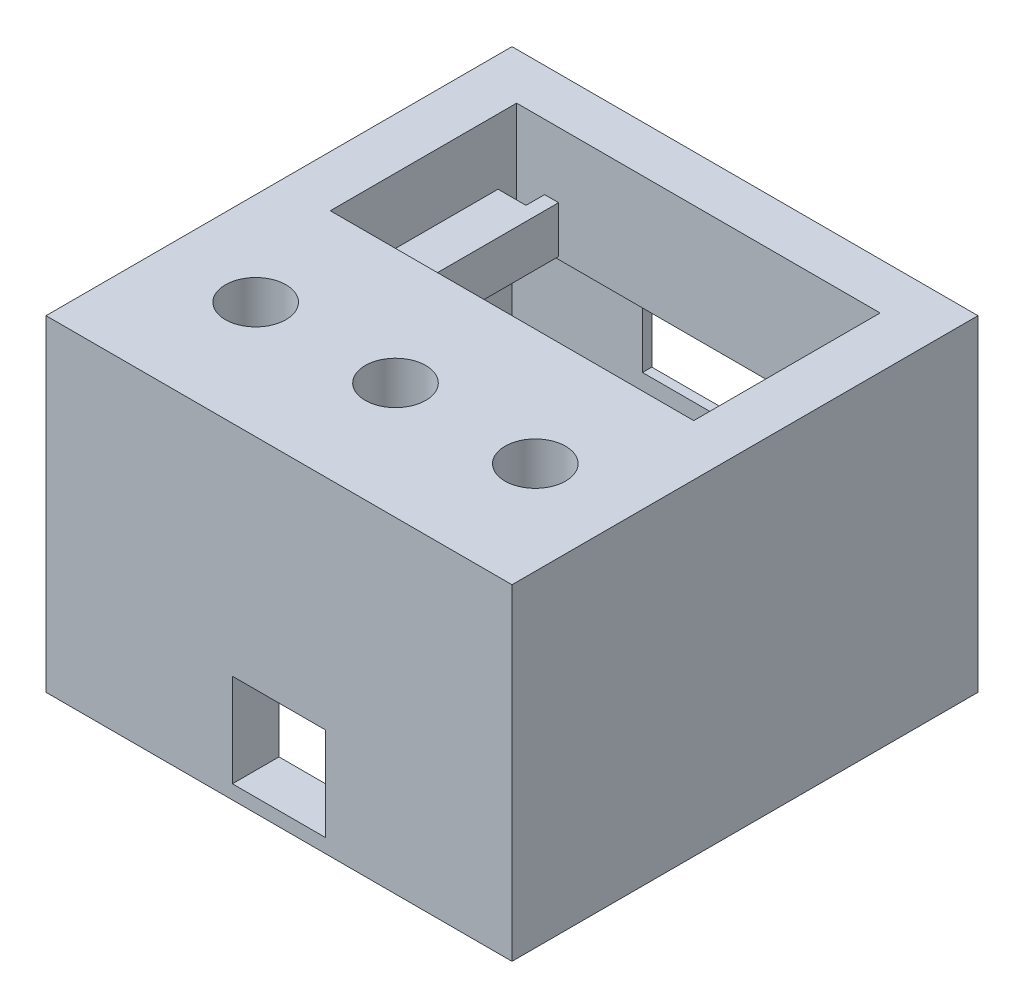
SolidWorks part; units mm, degrees
ref_plane "Front Plane" through (0, 0, 0) normal (0, 0, 1) x (1, 0, 0)
ref_plane "Top Plane" through (0, 0, 0) normal (0, 1, 0) x (1, 0, 0)
ref_plane "Right Plane" through (0, 0, 0) normal (1, 0, 0) x (0, 0, -1)
sketch "Sketch2" plane through (0, 0, 0) normal (0, 1, 0) x (1, 0, 0)
  line L0 (0, 0) -> (0, 25)
  line L1 (-25, 25) -> (25, 25)
  line L2 (-25, 25) -> (-25, -25)
  line L3 (-25, -25) -> (25, -25)
  line L4 (25, 25) -> (25, -25)
  line L5 (-25, 25) -> (25, -25) construction
  line L6 (-25, -25) -> (25, 25) construction
  point P0 (0, 0)
  dimension "D1" = 50
  dimension "D2" = 50
extrude "Boss-Extrude1" add sketch "Sketch2" against normal blind 40 contours L4 L1 L2 L3 region at (-12.5, 0, -24.2929)
sketch "Sketch3" plane through (0, 0, 0) normal (0, 1, 0) x (1, 0, 0)
  line L0 (0, 25) -> (0, 20)
  line L1 (-25, 25) -> (25, 25) construction
  line L2 (0, 20) -> (19.5, 20)
  line L3 (0, 20) -> (-19.5, 20)
  line L4 (-19.5, 20) -> (-19.5, 0)
  line L5 (-19.5, 0) -> (19.5, 0)
  line L6 (19.5, 20) -> (19.5, 0)
sketch "Sketch4" plane through (0, 0, 0) normal (0, 1, 0) x (1, 0, 0)
  line L0 (0, 0) -> (0, -25)
  line L1 (-25, -25) -> (25, -25) construction
  line L2 (0, -12.5) -> (15, -12.5)
  line L3 (0, -12.5) -> (-15, -12.5)
  line L4 (-15, -12.5) -> (-15, -25)
  circle A0 centre (15, -12.5) radius 3.25
  circle A1 centre (-15, -12.5) radius 3.25
  circle A2 centre (0, -12.5) radius 3.25
extrude "Cut-Extrude1" cut sketch "Sketch4" against normal blind 6 contours L0 A2 L3 | L2 A2 L0 | L0 A2 L2 | L3 A2 L0 | A0 | A1 region at (1.3793, 0, 11.1207) region at (15, 0, 9.3419) region at (-1.3793, 0, 11.1207) region at (1.3793, 0, 13.8793) region at (-1.3793, 0, 13.8793)
sketch "Sketch5" plane through (0, -40, 0) normal (0, -1, 0) x (1, 0, 0)
  line L0 (-15, 12.5) -> (-19, 12.5)
  line L1 (-15, 12.5) -> (-11, 12.5)
  line L2 (0, 12.5) -> (-15, 12.5) construction
  line L3 (0, 12.5) -> (-4, 12.5)
  line L4 (0, 0) -> (0, 25) construction
  line L5 (0, 12.5) -> (4, 12.5)
  line L6 (0, 12.5) -> (15, 12.5) construction
  line L7 (4, 12.5) -> (4, 19)
  line L8 (4, 12.5) -> (4, 6)
  line L9 (4, 6) -> (-4, 6)
  line L10 (-4, 6) -> (-4, 19)
  line L11 (-4, 19) -> (4, 19)
  line L12 (15, 12.5) -> (11, 12.5)
  line L13 (15, 12.5) -> (19, 12.5)
  line L14 (19, 12.5) -> (19, 19)
  line L15 (19, 19) -> (11, 19)
  line L16 (11, 19) -> (11, 6)
  line L17 (11, 6) -> (19, 6)
  line L18 (19, 6) -> (19, 12.5)
  line L19 (-11, 12.5) -> (-11, 19)
  line L20 (-11, 19) -> (-19, 19)
  line L21 (-19, 19) -> (-19, 6)
  line L22 (-19, 6) -> (-11, 6)
  line L23 (-11, 6) -> (-11, 12.5)
extrude "Cut-Extrude2" cut sketch "Sketch5" against normal blind 34 contours L17 L18 L13 L12 L16 | L15 L16 L12 L13 L14 | L22 L23 L1 L0 L21 | L20 L21 L0 L1 L19 | L8 L9 L10 L11 L7 region at (-15, -40, 9.25) region at (-15, -40, 15.75) region at (15, -40, 9.25) region at (15, -40, 15.75)
sketch "Sketch6" plane through (0, -40, 0) normal (0, -1, 0) x (1, 0, 0)
  line L0 (-25, 25) -> (25, 25)
  line L1 (25, 25) -> (25, -25)
  line L2 (25, -25) -> (-25, -25)
  line L3 (-25, -25) -> (-25, 25)
  line L4 (-20, -20) -> (-20, 20)
  line L5 (-20, 20) -> (20, 20)
  line L6 (20, 20) -> (20, -20)
  line L7 (20, -20) -> (-20, -20)
  line L8 (0, 0) -> (0, 6)
  line L9 (4, 6) -> (-4, 6) construction
  line L10 (0, 3) -> (20, 3)
  line L11 (0, 3) -> (-20, 3)
  line M9 (19, 19) -> (19, 6)
  line M10 (19, 6) -> (11, 6)
  line M11 (11, 6) -> (11, 19)
  line M12 (11, 19) -> (19, 19)
  line M13 (-11, 19) -> (-11, 6)
  line M14 (-11, 6) -> (-19, 6)
  line M15 (-19, 6) -> (-19, 19)
  line M16 (-19, 19) -> (-11, 19)
  line M21 (4, 19) -> (4, 6)
  line M22 (4, 6) -> (-4, 6)
  line M23 (-4, 6) -> (-4, 19)
  line M24 (-4, 19) -> (4, 19)
  dimension "D1" = 5
extrude "Cut-Extrude3" cut sketch "Sketch6" against normal blind 24 contours L11 L10 L6 L5 L4 M22 M23 M24 M21 M16 M13 M14 M15 M12 M9 M10 M11 region at (-19.5654, -40, 11.5)
extrude "Cut-Extrude4" cut sketch "Sketch3" against normal blind 7 contours L6 L2 L3 L4 L5 region at (0, 0, -10)
sketch "Sketch7" plane through (0, -7, 0) normal (0, 1, 0) x (1, 0, 0)
  line L0 (-19.5, 20) -> (-16.5, 20)
  line L1 (-19.5, 20) -> (19.5, 20) construction
  line L2 (-16.5, 20) -> (-16.5, 18)
  line L3 (-16.5, 18) -> (-19.5, 18)
  line L4 (-19.5, 20) -> (-19.5, 0) construction
  line L5 (-19.5, 18) -> (-19.5, 20)
  line L6 (-19.5, 0) -> (-19.5, 2)
  line L7 (-19.5, 20) -> (-19.5, 0) construction
  line L8 (-19.5, 2) -> (-16.5, 2)
  line L9 (-16.5, 2) -> (-16.5, 0)
  line L10 (-19.5, 0) -> (19.5, 0) construction
  line L11 (-16.5, 0) -> (-19.5, 0)
  line L12 (19.5, 0) -> (19.5, 2)
  line L13 (19.5, 20) -> (19.5, 0) construction
  line L14 (19.5, 2) -> (16.5, 2)
  line L15 (16.5, 2) -> (16.5, 0)
  line L16 (-19.5, 0) -> (19.5, 0) construction
  line L17 (16.5, 0) -> (19.5, 0)
  line L18 (19.5, 20) -> (16.5, 20)
  line L19 (-19.5, 20) -> (19.5, 20) construction
  line L20 (16.5, 20) -> (16.5, 18)
  line L21 (16.5, 18) -> (19.5, 18)
  line L22 (19.5, 18) -> (19.5, 20)
sketch "Sketch8" plane through (0, -40, 0) normal (0, -1, 0) x (1, 0, 0)
  line L0 (-20, 3) -> (-20, -25)
  line L1 (-25, -25) -> (25, -25) construction
  line L2 (-20, -25) -> (-20, -20)
  line L3 (20, 3) -> (20, -25)
  line L4 (20, -25) -> (20, -20)
  line L5 (20, -20) -> (-20, -20)
  line L6 (0, -20) -> (0, 0)
  line L7 (0, 0) -> (20, 0)
  line L8 (20, 0) -> (-20, 0)
  line L9 (0, -20) -> (-15, -20)
  line L10 (-15, -20) -> (-15, 0)
  line L11 (-15, 0) -> (15, 0)
  line L12 (15, 0) -> (15, -20)
  line L13 (15, -20) -> (-15, -20)
  line L14 (-20, 3) -> (20, 3)
  line M9 (20, 3) -> (-20, 3)
extrude "Cut-Extrude5" cut sketch "Sketch8" against normal blind 33 contours L10 L5 L6 L8 | L12 L7 L6 L5 region at (-7.5, -40, -10) region at (7.5, -40, -10)
extrude "Cut-Extrude6" cut sketch "Sketch8<3>" against normal blind 24 contours L5 L10 L8 L0 | L8 L12 L5 L3 region at (-17.5, -40, -10) region at (17.5, -40, -10)
sketch "Sketch8<3>" plane through (0, -40, 0) normal (0, -1, 0) x (1, 0, 0) same geometry as "Sketch8"
extrude "Cut-Extrude7" cut sketch "Sketch8<4>" against normal blind 24 contours L8 L7 L3 L0 M9 region at (0, -40, 1.5)
sketch "Sketch8<4>" plane through (0, -40, 0) normal (0, -1, 0) x (1, 0, 0) same geometry as "Sketch8"
extrude "Cut-Extrude8" cut sketch "Sketch7" against normal blind 10
sketch "Sketch9" plane through (0, -40, 0) normal (0, -1, 0) x (1, 0, 0)
  line L0 (-20, 20) -> (-25, 20)
  line L1 (-25, -25) -> (-25, 25) construction
  line L2 (-25, 20) -> (-25, 25)
  line L3 (-25, 25) -> (-20, 25)
  line L4 (-25, 25) -> (25, 25) construction
  line L5 (-20, 25) -> (-20, 20)
  line L6 (-20, -20) -> (-25, -20)
  line L7 (-25, -20) -> (-25, -25)
  line L8 (-25, -25) -> (-20, -25)
  line L9 (-25, -25) -> (25, -25) construction
  line L10 (-20, -25) -> (-20, -20)
  line L11 (0, 0) -> (0, 3.3941)
  line L12 (15, 0) -> (-15, 0) construction
  line L13 (0, 0) -> (0, 25) construction
  line L22 (-20, 20) -> (-21, 20)
  line L23 (-25, 22.5) -> (-22.5, 22.5)
  line L24 (-20, 20) -> (-20, 21)
  line L25 (-20, -22.5) -> (-22.5, -22.5)
  line L26 (-20, -25) -> (-20, -24)
  line L27 (20, -25) -> (20, -24)
  line L28 (20, -22.5) -> (22.5, -22.5)
  line L29 (20, 20) -> (20, 21)
  line L30 (25, 22.5) -> (22.5, 22.5)
  line L31 (20, 20) -> (21, 20)
  line L32 (20, -25) -> (20, -20)
  line L33 (25, -25) -> (20, -25)
  line L34 (25, -20) -> (25, -25)
  line L35 (20, -20) -> (25, -20)
  line L36 (20, 25) -> (20, 20)
  line L37 (25, 25) -> (20, 25)
  line L38 (25, 20) -> (25, 25)
  line L39 (20, 20) -> (25, 20)
  line L40 (-20, -25) -> (-21, -25)
  line L41 (-24, 24) -> (-21, 24)
  line L42 (-24, 24) -> (-24, 21)
  line L43 (-24, 21) -> (-21, 21)
  line L44 (-21, 24) -> (-21, 21)
  line L45 (-24, 24) -> (-21, 21) construction
  line L46 (-24, 21) -> (-21, 24) construction
  line L47 (20, -25) -> (21, -25)
  line L48 (-24, -21) -> (-21, -21)
  line L49 (-24, -21) -> (-24, -24)
  line L50 (-24, -24) -> (-21, -24)
  line L51 (-21, -21) -> (-21, -24)
  line L52 (-24, -21) -> (-21, -24) construction
  line L53 (-24, -24) -> (-21, -21) construction
  line L55 (24, -21) -> (21, -21)
  line L56 (24, -21) -> (24, -24)
  line L57 (24, -24) -> (21, -24)
  line L58 (21, -21) -> (21, -24)
  line L59 (24, -21) -> (21, -24) construction
  line L60 (24, -24) -> (21, -21) construction
  line L61 (24, 24) -> (21, 24)
  line L62 (24, 24) -> (24, 21)
  line L63 (24, 21) -> (21, 21)
  line L64 (21, 24) -> (21, 21)
  line L65 (24, 24) -> (21, 21) construction
  line L66 (24, 21) -> (21, 24) construction
  dimension "D1" = 1
extrude "Cut-Extrude9" cut sketch "Sketch9" against normal blind 10 contours L44 L41 L42 L43 | L61 L64 L63 L62 | L55 L58 L57 L56 | L51 L48 L49 L50 region at (-23.9576, -40, 23.25) region at (-21.0424, -40, -23.25) region at (21.0424, -40, -21.75) region at (23.9576, -40, 21.75)
sketch "Sketch11" plane through (0, 0, 25) normal (0, 0, 1) x (1, 0, 0)
  line L0 (0, 0) -> (0, -17)
  line L1 (0, -17) -> (0, -40)
  line L2 (-25, -40) -> (25, -40) construction
  line L4 (-5, -23.5) -> (5, -23.5)
  line L5 (-5, -23.5) -> (-5, -33.5)
  line L6 (-5, -33.5) -> (5, -33.5)
  line L7 (5, -23.5) -> (5, -33.5)
  line L8 (-5, -23.5) -> (5, -33.5) construction
  line L9 (-5, -33.5) -> (5, -23.5) construction
  point P6 (0, -28.5)
  dimension "D1" = 10
  dimension "D2" = 10
sketch "Sketch12" plane through (0, -40, 0) normal (0, -1, 0) x (1, 0, 0)
  line L0 (-25, 25) -> (25, 25)
  line L1 (25, 25) -> (25, -25)
  line L2 (25, -25) -> (-25, -25)
  line L3 (-25, -25) -> (-25, 25) construction
  line L4 (-25, -25) -> (25, -25) construction
  line L5 (-25, -25) -> (-25, 25)
extrude "Cut-Extrude10" cut sketch "Sketch12" against normal blind 5
sketch "Sketch13" plane through (0, 0, -25) normal (0, 0, -1) x (-1, 0, 0)
  line L0 (-25, 0) -> (-25, -40)
  line L1 (-25, -40) -> (0, -40)
  line L2 (0, -40) -> (0, -19.2799)
  line L3 (0, -17) -> (0, -40) construction
  line L4 (0, -19.2799) -> (0, -22.2799)
  line L5 (0, -19.2799) -> (0, -16.2799)
  line L6 (0, 0) -> (0, -17) construction
  line L7 (0, -16.2799) -> (10, -16.2799)
  line L8 (10, -16.2799) -> (10, -22.2799)
  line L9 (10, -22.2799) -> (-10, -22.2799)
  line L10 (-10, -22.2799) -> (-10, -16.2799)
  line L11 (-10, -16.2799) -> (0, -16.2799)
sketch "Sketch14" plane through (0, 0, -20) normal (0, 0, 1) x (1, 0, 0)
  line L0 (10, -19.2799) -> (10, -12.2799)
  line L1 (10, -22.2799) -> (10, -16.2799) construction
  line L2 (10, -19.2799) -> (10, -36.2799)
  line L3 (10, -36.2799) -> (-20, -36.2799)
  line L4 (-20, -36.2799) -> (-20, -12.2799)
  line L5 (-20, -12.2799) -> (10, -12.2799)
sketch "Sketch16" plane through (0, -16, 0) normal (0, -1, 0) x (1, 0, 0)
  line L0 (15, -20) -> (15, 0)
  line L1 (15, 0) -> (20, 0)
  line L2 (20, 20) -> (20, -20) construction
  line L3 (20, 0) -> (20, -20)
  line L4 (20, -20) -> (15, -20)
  line L5 (-15, 0) -> (-20, 0)
  line L6 (-20, -20) -> (-20, 20) construction
  line L7 (-20, 0) -> (-20, -20)
  line L8 (-20, -20) -> (-15, -20)
  line L9 (-15, -20) -> (-15, 0)
extrude "Cut-Extrude11" cut sketch "Sketch16" against normal blind 4
extrude "Cut-Extrude12" cut sketch "Sketch13" against normal blind 5 contours L7 L8 L9 L10 L11
extrude "Cut-Extrude13" cut sketch "Sketch14" against normal blind 4
sketch "Sketch18" plane through (-20, 0, 0) normal (1, 0, 0) x (0, 0, -1)
  line L0 (24, -35) -> (24, -12.2799)
  line L1 (24, -35) -> (24, -29)
  line L2 (24, -29) -> (4, -29)
  line L3 (4, -29) -> (4, -12.2799)
  line L4 (4, -12.2799) -> (24, -12.2799)
  line M3 (24, -12.2799) -> (20, -12.2799)
extrude "Cut-Extrude14" cut sketch "Sketch18" against normal blind 4 contours L4 L3 L2 L0 M3 region at (-20, -20.6399, -14)
extrude "Cut-Extrude15" cut sketch "Sketch11" against normal blind 5 contours L7 L4 L1 L6 | L5 L6 L1 L4 region at (2.5, -28.5, 25) region at (-2.5, -28.5, 25)
sketch "Sketch20" plane through (0, -35, 0) normal (0, -1, 0) x (1, 0, 0)
  circle A0 centre (15, 12.5) radius 6.5
  circle A1 centre (0, 12.5) radius 6.5
  circle A2 centre (-15, 12.5) radius 6.5
  line M5 (-20, -24) -> (-20, 20)
extrude "Cut-Extrude16" cut sketch "Sketch20" against normal blind 29 contours A1 | A2 M5 | A2 M5 | A0 region at (0, -35, 12.5) region at (-14.6155, -35, 12.5) region at (-20.6064, -35, 12.5)
